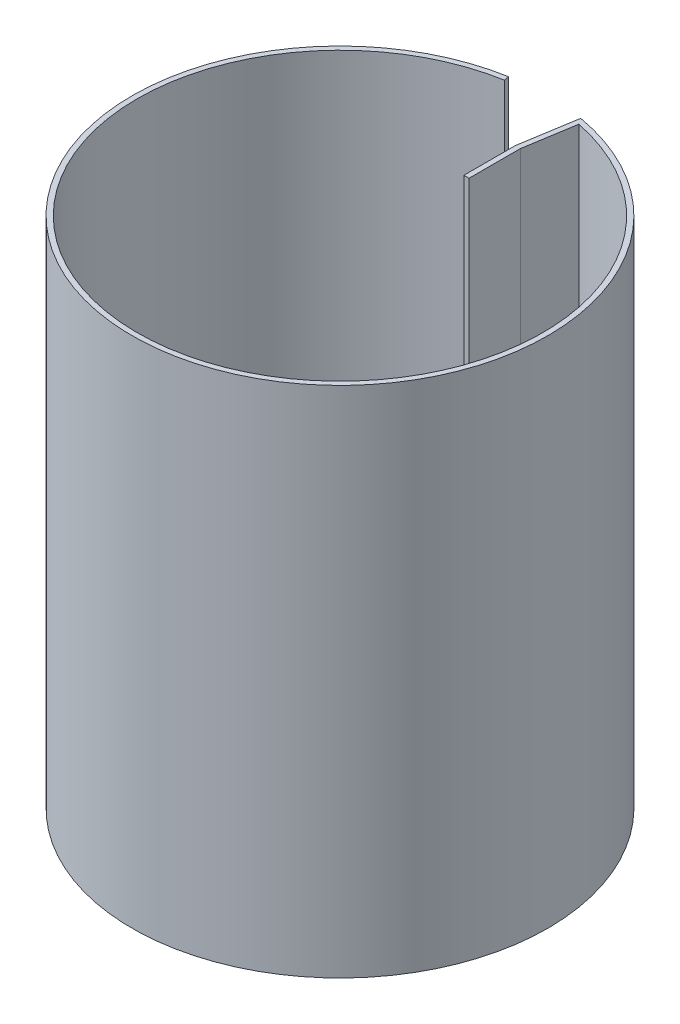
SolidWorks part; units mm, degrees
ref_plane "Plano frontal" through (0, 0, 0) normal (0, 0, 1) x (1, 0, 0)
ref_plane "Plano superior" through (0, 0, 0) normal (0, 1, 0) x (1, 0, 0)
ref_plane "Plano direito" through (0, 0, 0) normal (1, 0, 0) x (0, 0, -1)
sketch "Esboço1" plane through (0, 0, 0) normal (0, 1, 0) x (1, 0, 0)
  line L0 (0, 97.5906) -> (0, -93.5714) construction
  line L1 (-13.7182, 77.7998) -> (-14.0655, 79.7694)
  line L2 (13.7182, 77.7998) -> (14.0655, 79.7694)
  line L4 (12.5, 37.8) -> (12.5, 57.8)
  line L5 (10.5, 37.8) -> (10.5, 57.8)
  line L6 (10.5, 57.8) -> (13.7182, 77.7998)
  line L7 (12.5, 57.8) -> (15.6591, 77.4325)
  line L8 (12.5, 37.8) -> (10.5, 37.8)
  arc A0 (-14.0655, 79.7694) -> (14.0655, 79.7694) centre (0, 0) ccw
  arc A1 (-13.7182, 77.7998) -> (15.6591, 77.4325) centre (0, 0) ccw
  dimension "D1" = 10
  dimension "D3" = 81
  dimension "D4" = 79
  dimension "D2" = 10
  dimension "D5" = 2
  dimension "D6" = 1.9746
  dimension "D7" = 20
  dimension "D8" = 19.6325
extrude "Ressalto-extrusão1" add sketch "Esboço1" along normal blind 200
